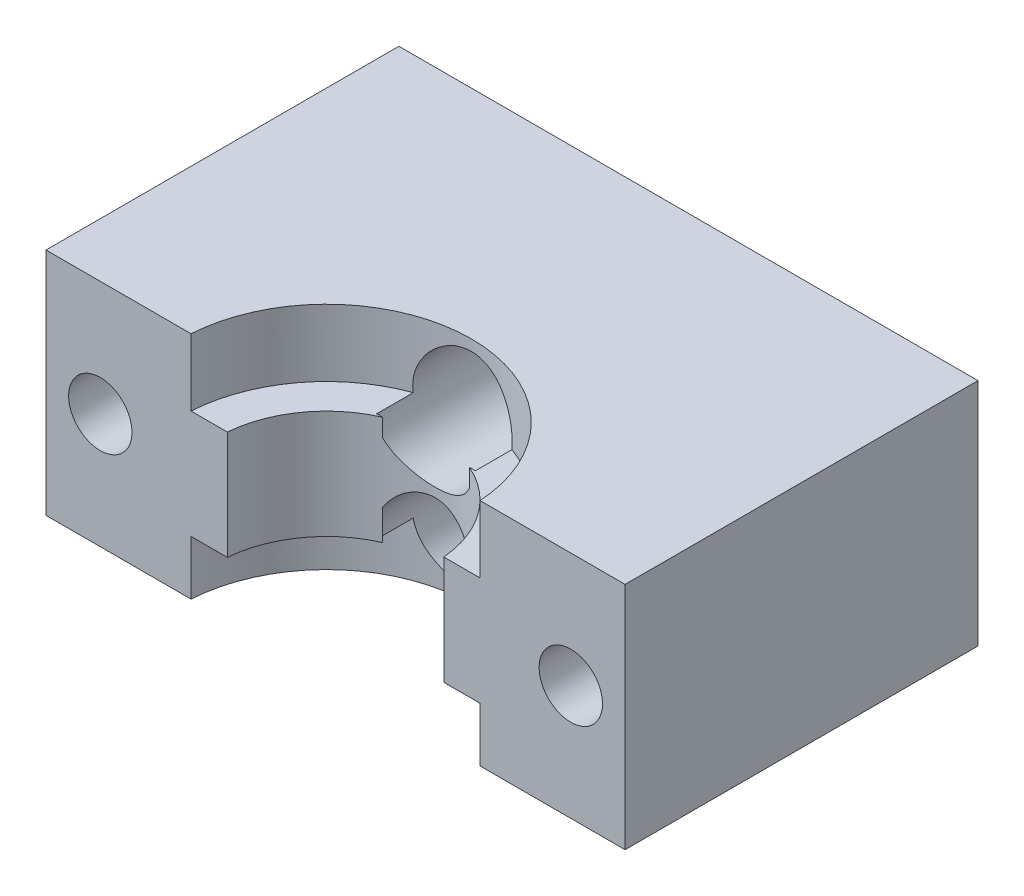
SolidWorks part; units mm, degrees
ref_plane "Front Plane" through (0, 0, 0) normal (0, 0, 1) x (1, 0, 0)
ref_plane "Top Plane" through (0, 0, 0) normal (0, 1, 0) x (1, 0, 0)
ref_plane "Right Plane" through (0, 0, 0) normal (1, 0, 0) x (0, 0, -1)
sketch "Sketch2" plane through (0, 0, 0) normal (0, 0, 1) x (1, 0, 0)
  line L0 (0, -3) -> (0, 3) construction
  line L1 (-16, 6.35) -> (16, 6.35)
  line L2 (-16, 6.35) -> (-16, -6.35)
  line L3 (-16, -6.35) -> (16, -6.35)
  line L4 (16, 6.35) -> (16, -6.35)
  line L5 (-16, 6.35) -> (16, -6.35) construction
  line L6 (-16, -6.35) -> (16, 6.35) construction
  circle A0 centre (0, 3) radius 1.75
  circle A1 centre (0, -3) radius 1.75
  point P0 (0, 0)
  dimension "D3" = 3.5
  dimension "D1" = 32
  dimension "D2" = 12.7
  dimension "D4" = 6
extrude "Boss-Extrude1" add sketch "Sketch2" along normal blind 19.5
sketch "Sketch3" plane through (0, 0, 19.5) normal (0, 0, 1) x (1, 0, 0)
  line L0 (16, 6.35) -> (-16, 6.35) construction
  line L5 (-16, -6.35) -> (16, -6.35) construction
  line L6 (-16, 6.35) -> (-10, 6.35) construction
  line L7 (-13, 6.35) -> (-13, -6.35) construction
  line L8 (10, 6.35) -> (16, 6.35) construction
  line L9 (13, 6.35) -> (13, -6.35) construction
  circle A0 centre (-13, 0) radius 1.75
  circle A1 centre (13, 0) radius 1.75
  dimension "D2" = 3.5
  dimension "D1" = 6
  dimension "D3" = 6
extrude "Cut-Extrude1" cut sketch "Sketch3" against normal through all
sketch "Sketch4" plane through (0, 0, 0) normal (0, 0, -1) x (-1, 0, 0)
  line L1 (-10.5, -1.4434) -> (-10.5, 1.4434)
  line L2 (-10.5, 1.4434) -> (-13, 2.8868)
  line L3 (-13, 2.8868) -> (-15.5, 1.4434)
  line L4 (-15.5, 1.4434) -> (-15.5, -1.4434)
  line L5 (-15.5, -1.4434) -> (-13, -2.8868)
  line L6 (-13, -2.8868) -> (-10.5, -1.4434)
  line L7 (13, -2.8868) -> (15.5, -1.4434)
  line L8 (15.5, -1.4434) -> (15.5, 1.4434)
  line L9 (15.5, 1.4434) -> (13, 2.8868)
  line L10 (13, 2.8868) -> (10.5, 1.4434)
  line L11 (10.5, 1.4434) -> (10.5, -1.4434)
  line L12 (10.5, -1.4434) -> (13, -2.8868)
  line L13 (-16, -6.35) -> (-16, 6.35) construction
  circle A0 centre (-13, 0) radius 2.5 construction
  circle A1 centre (13, 0) radius 2.5 construction
  dimension "D1" = 5
extrude "Cut-Extrude2" cut sketch "Sketch4" against normal blind 4
sketch "Sketch5" plane through (0, 6.35, 0) normal (0, 1, 0) x (1, 0, 0)
  line L0 (16, 0) -> (-16, 0) construction
  circle A0 centre (0, -20) radius 8
  dimension "D1" = 16
  dimension "D2" = 20
extrude "Cut-Extrude3" cut sketch "Sketch5" against normal blind 3.7
sketch "Sketch9" plane through (0, 2.65, 0) normal (0, 1, 0) x (1, 0, 0)
  circle A0 centre (0, -20) radius 6
  dimension "D1" = 12
extrude "Cut-Extrude5" cut sketch "Sketch9" against normal blind 6
sketch "Sketch10" plane through (0, -3.35, 0) normal (0, 1, 0) x (1, 0, 0)
  circle A0 centre (0, -20) radius 8
  dimension "D1" = 16
extrude "Cut-Extrude6" cut sketch "Sketch10" against normal through all
ref_plane "Plane1" through (0, 0, 14.5) normal (0, 0, 1) x (1, 0, 0)
sketch "Sketch6" plane through (0, 0, 14.5) normal (0, 0, 1) x (1, 0, 0)
  circle A0 centre (0, 3) radius 2.75
  circle A1 centre (0, -3) radius 2.75
  dimension "D1" = 5.5
  dimension "D2" = 5.5
extrude "Cut-Extrude4" cut sketch "Sketch6" against normal blind 7.5
